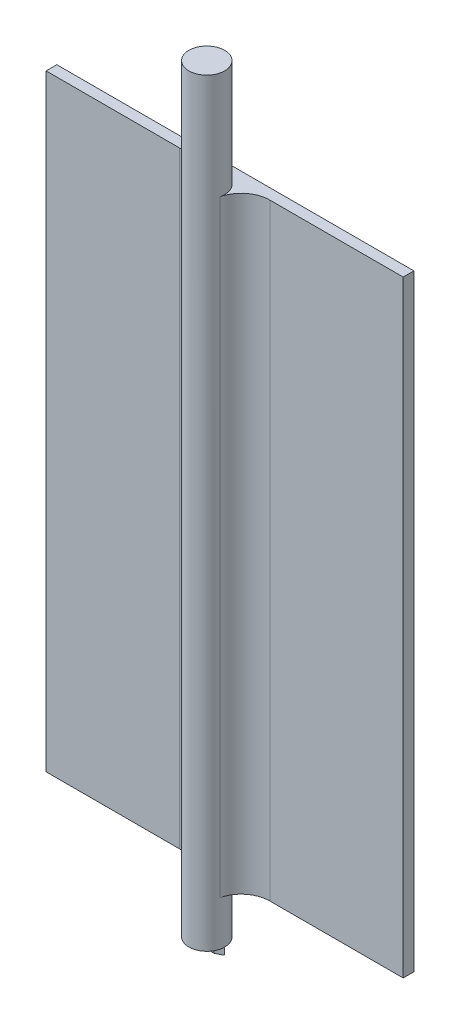
SolidWorks part; units mm, degrees
ref_plane "前视基准面" through (0, 0, 0) normal (0, 0, 1) x (1, 0, 0)
ref_plane "上视基准面" through (0, 0, 0) normal (0, 1, 0) x (1, 0, 0)
ref_plane "右视基准面" through (0, 0, 0) normal (1, 0, 0) x (0, 0, -1)
sketch "草图1" plane through (0, 0, 0) normal (0, 0, 1) x (1, 0, 0)
  line L1 (0, 0) -> (100, 0)
  line L2 (0, 0) -> (0, 170)
  line L3 (0, 170) -> (100, 170)
  line L4 (100, 0) -> (100, 170)
  dimension "D1" = 170
  dimension "D2" = 100
extrude "凸台-拉伸1" add sketch "草图1" along normal blind 3
sketch "草图2" plane through (0, 170, 0) normal (0, 1, 0) x (1, 0, 0)
  line L0 (100, -3) -> (0, -3) construction
  line L1 (45, -8) -> (45, -3)
  line L2 (55, -8) -> (55, -3)
  line L3 (45, -3) -> (55, -3)
  line L4 (100, -3) -> (100, 0) construction
  arc A0 (45, -8) -> (55, -8) centre (50, -8) ccw
  dimension "D1" = 10
  dimension "D2" = 5
  dimension "D3" = 50
extrude "凸台-拉伸2" add sketch "草图2" against normal up to surface (170 mm away) up to face at (50, 0, 1.5)
sketch "草图3" plane through (0, 170, 0) normal (0, 1, 0) x (1, 0, 0)
  circle A0 centre (50, -8) radius 5
extrude "凸台-拉伸3" add sketch "草图3" along normal blind 30
sketch "草图4" plane through (0, 0, 0) normal (0, -1, 0) x (1, 0, 0)
  circle A0 centre (50, 8) radius 5
  dimension "D1" = 10
extrude "凸台-拉伸4" add sketch "草图4" along normal blind 12.5
fillet "圆角1" radius 8 2 edges at (55, 85, 3) (45, 85, 3)
sketch "草图5" plane through (0, -12.5, 0) normal (0, -1, 0) x (1, 0, 0)
  line L0 (47, 9) -> (45, 8)
  line L1 (47, 7) -> (53, 7)
  line L3 (47, 9) -> (53, 9)
  line L7 (45, 8) -> (47, 7)
  line L8 (53, 9) -> (55, 8)
  line L9 (55, 8) -> (53, 7)
  circle A0 centre (50, 8) radius 5 construction
  arc A1 (45.135, 9.1538) -> (54.865, 9.1538) centre (50, 8) ccw construction
  point P0 (50, 8)
  dimension "D1" = 6
  dimension "D2" = 2
extrude "凸台-拉伸5" add sketch "草图5" along normal blind 2
